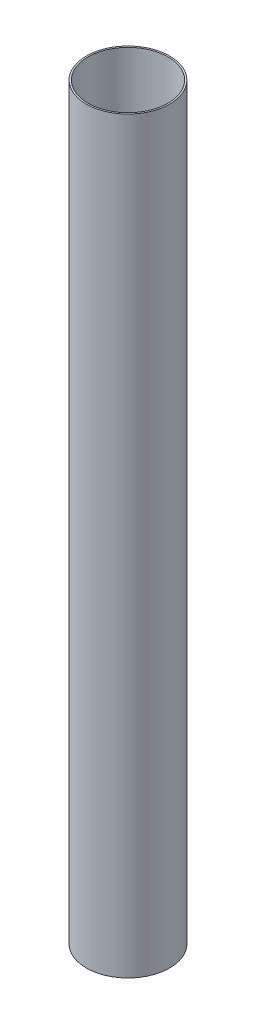
SolidWorks part; units mm, degrees
material "E-Glass Fiber"
ref_plane "Front Plane" through (0, 0, 0) normal (0, 0, 1) x (1, 0, 0)
ref_plane "Top Plane" through (0, 0, 0) normal (0, 1, 0) x (1, 0, 0)
ref_plane "Right Plane" through (0, 0, 0) normal (1, 0, 0) x (0, 0, -1)
sketch "Sketch1" plane through (0, 0, 0) normal (0, 1, 0) x (1, 0, 0)
  circle A0 centre (0, 0) radius 39.624
  circle A1 centre (0, 0) radius 38.1
  dimension "D1" = 79.248
  dimension "D2" = 76.2
extrude "Tube Extrusion" add sketch "Sketch1" along normal blind 711.2
